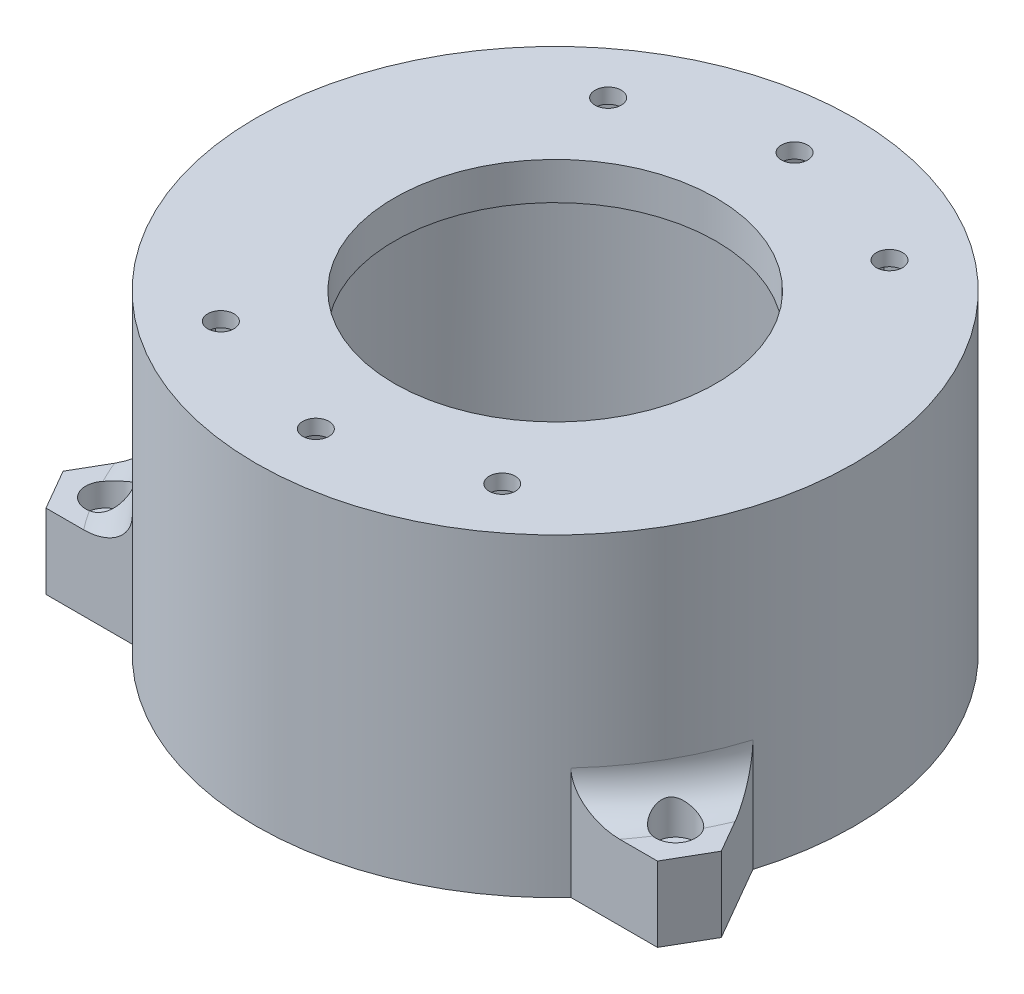
SolidWorks part; units mm, degrees
material "自定义塑料"
ref_plane "前视基准面" through (0, 0, 0) normal (0, 0, 1) x (1, 0, 0)
ref_plane "上视基准面" through (0, 0, 0) normal (0, 1, 0) x (1, 0, 0)
ref_plane "右视基准面" through (0, 0, 0) normal (1, 0, 0) x (0, 0, -1)
other "Configuration Table"
sketch "草图1" plane through (0, 0, 0) normal (0, 0, 1) x (1, 0, 0)
  line L0 (40, 39) -> (0, 39)
  line L1 (0, 39) -> (0, 0)
  line L2 (0, 0) -> (40, 0)
  line L3 (40, 0) -> (40, 39)
  line L4 (0, 39) -> (0, 0) construction
  dimension "D1" = 40
  dimension "D2" = 39
revolve "旋转1" add sketch "草图1" angle 360 about L4 reverse direction yes
hole_wizard "M64 六角头螺栓的柱形沉头孔1" positions "草图3" profile "草图2" counterbore size "M64" standard "ANSI Metric"
sketch "草图3" plane through (0, 39, 0) normal (0, 1, 0) x (1, 0, 0)
  point P0 (0, 0)
sketch "草图2" plane through (0, 39, 0) normal (1, 0, 0) x (0, 0, 1)
  line L0 (0, 0) -> (0, 39)
  line L1 (0, 39) -> (37, 39)
  line L2 (37, 39) -> (37, 5)
  line L3 (37, 5) -> (21.5, 5)
  line L4 (21.5, 5) -> (21.5, 0)
  line L5 (21.5, 0) -> (0, 0)
  line L10 (0, 39) -> (-37, 39) construction
  line L11 (0, -6.35) -> (0, 107.95) construction
  dimension "孔直径" = 74
  dimension "孔深度" = 39
  dimension "柱形沉头孔直径" = 43
  dimension "柱形沉头孔深度" = 5
  dimension "导头角度" = 180
sketch "草图4" plane through (0, 34, 0) normal (0, -1, 0) x (1, 0, 0)
  line L0 (16.1, 27.8568) -> (15.75, 24.5265)
  line L1 (15.75, 24.5265) -> (18.4591, 22.5583)
  line L2 (18.4591, 22.5583) -> (21.5182, 23.9203)
  line L3 (21.5182, 23.9203) -> (21.8683, 27.2506)
  line L4 (21.8683, 27.2506) -> (19.1592, 29.2188)
  line L5 (19.1592, 29.2188) -> (16.1, 27.8568)
extrude "切除-拉伸1" cut sketch "草图4" against normal blind 3
sketch "草图5" plane through (0, 34, 0) normal (0, -1, 0) x (1, 0, 0)
  line L0 (-21.8683, 27.2506) -> (-21.5182, 23.9203)
  line L1 (-21.5182, 23.9203) -> (-18.4591, 22.5583)
  line L2 (-18.4591, 22.5583) -> (-15.75, 24.5265)
  line L3 (-15.75, 24.5265) -> (-16.1, 27.8568)
  line L4 (-16.1, 27.8568) -> (-19.1592, 29.2188)
  line L5 (-19.1592, 29.2188) -> (-21.8683, 27.2506)
extrude "切除-拉伸2" cut sketch "草图5" against normal blind 3
sketch "草图6" plane through (0, 34, 0) normal (0, -1, 0) x (1, 0, 0)
  line L0 (-18.4591, -22.5583) -> (-21.5182, -23.9203)
  line L1 (-21.5182, -23.9203) -> (-21.8683, -27.2506)
  line L2 (-21.8683, -27.2506) -> (-19.1592, -29.2188)
  line L3 (-19.1592, -29.2188) -> (-16.1, -27.8568)
  line L4 (-16.1, -27.8568) -> (-15.75, -24.5265)
  line L5 (-15.75, -24.5265) -> (-18.4591, -22.5583)
extrude "切除-拉伸3" cut sketch "草图6" against normal blind 3
sketch "草图7" plane through (0, 34, 0) normal (0, -1, 0) x (1, 0, 0)
  line L0 (1.6743, -29.1) -> (-1.6743, -29.1)
  line L1 (-1.6743, -29.1) -> (-3.3486, -32)
  line L2 (-3.3486, -32) -> (-1.6743, -34.9)
  line L3 (-1.6743, -34.9) -> (1.6743, -34.9)
  line L4 (1.6743, -34.9) -> (3.3486, -32)
  line L5 (3.3486, -32) -> (1.6743, -29.1)
extrude "切除-拉伸4" cut sketch "草图7" against normal blind 3
sketch "草图8" plane through (0, 34, 0) normal (0, -1, 0) x (1, 0, 0)
  line L0 (21.8683, -27.2506) -> (21.5182, -23.9203)
  line L1 (21.5182, -23.9203) -> (18.4591, -22.5583)
  line L2 (18.4591, -22.5583) -> (15.75, -24.5265)
  line L3 (15.75, -24.5265) -> (16.1, -27.8568)
  line L4 (16.1, -27.8568) -> (19.1592, -29.2188)
  line L5 (19.1592, -29.2188) -> (21.8683, -27.2506)
extrude "切除-拉伸5" cut sketch "草图8" against normal blind 3
sketch "草图9" plane through (0, 34, 0) normal (0, -1, 0) x (1, 0, 0)
  line L0 (-3.3486, 32) -> (-1.6743, 29.1)
  line L1 (-1.6743, 29.1) -> (1.6743, 29.1)
  line L2 (1.6743, 29.1) -> (3.3486, 32)
  line L3 (3.3486, 32) -> (1.6743, 34.9)
  line L4 (1.6743, 34.9) -> (-1.6743, 34.9)
  line L5 (-1.6743, 34.9) -> (-3.3486, 32)
extrude "切除-拉伸6" cut sketch "草图9" against normal blind 3
hole_wizard "Ø3.5 (3.5) 直径孔1" positions "草图11" profile "草图10" hole size "Ø3.5" standard "ANSI Metric"
sketch "草图11" plane through (0, 37, 0) normal (0, -1, 0) x (-1, 0, 0)
  point P0 (18.8091, 25.8885)
  point P1 (-18.8091, 25.8885)
  point P2 (0, 32)
  point P3 (18.8091, -25.8885)
  point P4 (-18.8091, -25.8885)
  point P5 (0, -32)
sketch "草图10" plane through (-18.8091, 37, -25.8885) normal (1, 0, 0) x (0, 0, -1)
  line L0 (0, 0) -> (0, 2)
  line L1 (0, 2) -> (1.75, 2)
  line L2 (1.75, 2) -> (1.75, 0)
  line L5 (1.75, 0) -> (0, 0)
  line L11 (0, -6.35) -> (0, 107.95) construction
  dimension "通孔孔直径" = 3.5
  dimension "通孔孔深度" = 2
sketch "草图14" plane through (0, 0, 0) normal (0, -1, 0) x (1, 0, 0)
  circle A0 centre (0, 0) radius 37 construction
  circle A1 centre (0, 0) radius 40
  circle A2 centre (0, 0) radius 40
  circle A3 centre (0, 0) radius 37
  dimension "D1" = 0
extrude "凸台-拉伸1" add sketch "草图14" along normal blind 3
sketch "草图15" plane through (0, -3, 0) normal (0, -1, 0) x (1, 0, 0)
  line L0 (0, 0) -> (37.7596, 21.8005) construction
  line L1 (0, 0) -> (60.0524, 0) construction
  line L2 (29.3273, 27.209) -> (38.2227, 11.791)
  line L3 (8.9, -39.0027) -> (-8.9, -38.9973)
  line L4 (38.2227, 11.791) -> (43.9984, 21.7906)
  line L5 (43.9984, 21.7906) -> (40.8751, 27.2042)
  line L6 (40.8751, 27.2042) -> (29.3273, 27.209)
  line L7 (-8.9, -38.9973) -> (-3.128, -48.9991)
  line L8 (-3.128, -48.9991) -> (3.122, -49.0009)
  line L9 (3.122, -49.0009) -> (8.9, -39.0027)
  line L10 (-38.2273, 11.7937) -> (-29.3227, 27.2063)
  line L11 (-29.3227, 27.2063) -> (-40.8704, 27.2085)
  line L12 (-40.8704, 27.2085) -> (-43.9971, 21.7968)
  line L13 (-43.9971, 21.7968) -> (-38.2273, 11.7937)
  circle A0 centre (0, 0) radius 40 construction
  arc A1 (-7.7071, -38.9977) -> (7.7071, -39.0023) centre (0, -39) ccw construction
  arc A2 (37.6265, 12.8243) -> (29.9234, 26.1757) centre (33.775, 19.5) ccw construction
  arc A3 (-29.9194, 26.1734) -> (-37.6306, 12.8266) centre (-33.775, 19.5) ccw construction
  point P3 (33.775, 19.5)
  point P10 (33.775, 19.5)
  point P18 (0, -39)
  point P22 (0, -39)
  point P27 (-33.775, 19.5)
  point P31 (-33.775, 19.5)
  point P36 (0, 0)
  dimension "D1" = 3
  dimension "D2" = 39
  dimension "D3" = 6.25
  dimension "17.8" = 17.8
  dimension "D4" = 10
extrude "凸台-拉伸2" add sketch "草图15" against normal blind 10
fillet "圆角1" radius 5 1 edges at (-0.0121, 7, -40)
fillet "圆角2" radius 5 2 edges at (-34.635, 7, 20.0105) (34.6471, 7, 19.9895)
sketch "草图20" plane through (0, -3, 0) normal (0, -1, 0) x (1, 0, 0)
  line L0 (-3.128, -48.9991) -> (3.122, -49.0009) construction
  circle A1 centre (0.0003, -44) radius 1.45
  circle A2 centre (-38.1053, 21.9998) radius 1.45
  circle A3 centre (38.105, 22.0002) radius 1.45
  point P10 (0, 0)
  dimension "D1" = 2.9
  dimension "D2" = 3
  dimension "5" = 5
extrude "切除-拉伸8" cut sketch "草图20" against normal up to next
sketch "草图21" plane through (0, 7, 0) normal (0, 1, 0) x (1, 0, 0)
  circle A0 centre (0, 0) radius 2.7508
  circle A1 centre (0, 0) radius 3.1216
  circle A2 centre (0.0003, 44) radius 2.66
  circle A3 centre (38.105, -22.0002) radius 2.66
  circle A4 centre (-38.1053, -21.9998) radius 2.66
  point P14 (0, 0)
  dimension "D1" = 5.32
  dimension "D2" = 3
extrude "切除-拉伸9" cut sketch "草图21" against normal blind 3.1 and the other way blind 10
